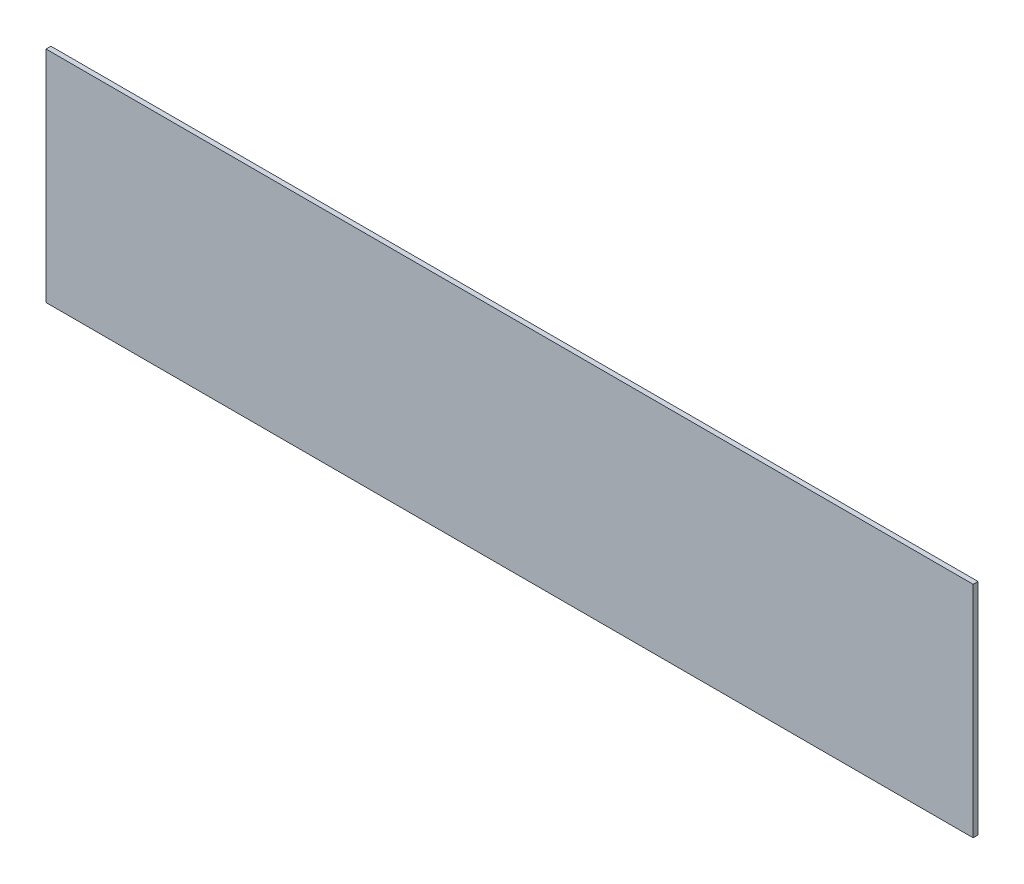
SolidWorks part; units mm, degrees
ref_plane "Ebene vorne" through (0, 0, 0) normal (0, 0, 1) x (1, 0, 0)
ref_plane "Ebene oben" through (0, 0, 0) normal (0, 1, 0) x (1, 0, 0)
ref_plane "Ebene rechts" through (0, 0, 0) normal (1, 0, 0) x (0, 0, -1)
sketch "Sketch2" plane through (0, 0, 0) normal (1, 0, 0) x (0, 0, -1)
  line L1 (0, 0) -> (2, 0)
  line L2 (0, 0) -> (0, 90)
  line L3 (0, 90) -> (2, 90)
  line L4 (2, 0) -> (2, 90)
  dimension "D1" = 2
  dimension "D2" = 90
extrude "Boss-Extrude1" add sketch "Sketch2" along normal blind 380
